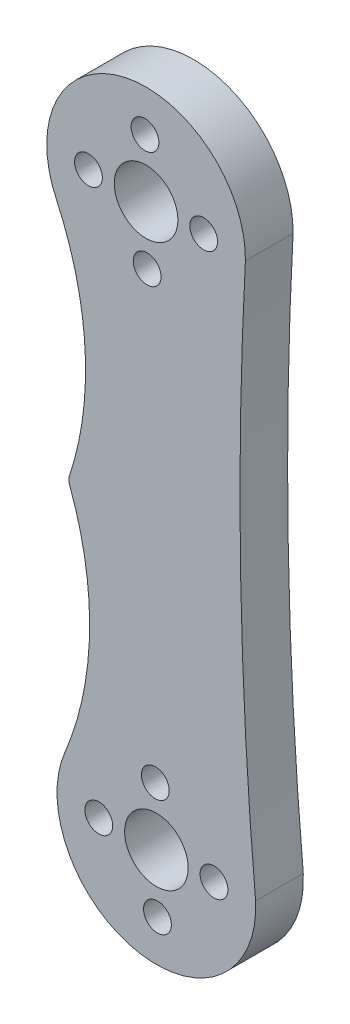
SolidWorks part; units mm, degrees
material "ABS"
ref_plane "Front Plane" through (0, 0, 0) normal (0, 0, 1) x (1, 0, 0)
ref_plane "Top Plane" through (0, 0, 0) normal (0, 1, 0) x (1, 0, 0)
ref_plane "Right Plane" through (0, 0, 0) normal (1, 0, 0) x (0, 0, -1)
sketch "Sketch1" plane through (0, 0, 0) normal (0, 0, 1) x (1, 0, 0)
  line L1 (-15, -50) -> (15, -50)
  line L2 (-15, -50) -> (-15, 50)
  line L3 (-15, 50) -> (15, 50)
  line L4 (15, -50) -> (15, 50)
  line L5 (-15, -50) -> (15, 50) construction
  line L6 (-15, 50) -> (15, -50) construction
  point P0 (0, 0)
  dimension "D1" = 100
  dimension "D2" = 30
extrude "Boss-Extrude1" add sketch "Sketch1" along normal blind 6
sketch "Sketch2" plane through (0, 0, 0) normal (0, 0, -1) x (-1, 0, 0)
  line L0 (-15, 50) -> (15, 50)
  line L1 (15, 50) -> (15, -50)
  line L2 (15, -50) -> (-15, -50)
  line L3 (-15, -50) -> (-15, 50)
  arc A0 (-11.5325, 35.4338) -> (13.1458, 32.8353) centre (0.9658, 35.6453) cw
  arc A1 (13.4636, 35.4133) -> (-11.5321, 35.8772) centre (0.9658, 35.6453) ccw construction
  arc A2 (12.3021, 30.3787) -> (13.4636, 35.4133) centre (0.9658, 35.6453) ccw construction
  arc A3 (13.1458, 32.8353) -> (12.3021, 30.3787) centre (0.9658, 35.6453) cw
  arc A4 (12.3021, 30.3787) -> (10.604, 0.9581) centre (48.5784, 13.5255) ccw
  arc A5 (8.5853, 14.2678) -> (10.604, 0.9581) centre (48.5784, 13.5255) ccw construction
  arc A6 (10.604, 0.9581) -> (10.5855, -0.037) centre (9.1799, 0.4868) cw
  arc A7 (10.5855, -0.037) -> (8.0744, -13.2627) centre (48.0675, -14.0049) ccw construction
  arc A8 (-12.815, -33.6676) -> (11.1908, -29.5004) centre (-0.3332, -34.3427) ccw
  arc A9 (-12.8311, -34.1107) -> (12.1646, -34.5746) centre (-0.3332, -34.3427) ccw construction
  arc A10 (12.1646, -34.5746) -> (11.1908, -29.5004) centre (-0.3332, -34.3427) ccw construction
  arc A11 (11.1908, -29.5004) -> (10.5855, -0.037) centre (48.0675, -14.0049) cw
  arc A13 (-11.5325, 35.4338) -> (-12.815, -33.6676) centre (-492.0571, 9.7897) cw
  arc A14 (-12.7832, -33.2253) -> (-12.8311, -34.1107) centre (-0.3332, -34.3427) ccw construction
  arc A15 (8.0744, -13.2627) -> (11.1908, -29.5004) centre (48.0675, -14.0049) ccw construction
  arc A16 (12.3021, 30.3787) -> (13.4636, 35.4133) centre (0.9658, 35.6453) ccw construction
  circle A17 centre (0.9658, 35.6453) radius 4
  circle A18 centre (1.1003, 42.894) radius 1.75
  circle A19 centre (8.2145, 35.5107) radius 1.75
  circle A20 centre (-6.283, 35.7798) radius 1.75
  circle A21 centre (0.8312, 28.3965) radius 1.75
  circle A22 centre (-0.3332, -34.3427) radius 4
  circle A23 centre (-0.1987, -27.0939) radius 1.75
  circle A24 centre (6.9155, -34.4772) radius 1.75
  circle A25 centre (-0.4677, -41.5914) radius 1.75
  circle A26 centre (-7.582, -34.2081) radius 1.75
  line M5 (-15, 50) -> (-15, -50)
  line M6 (-15, -50) -> (15, -50)
  line M7 (15, -50) -> (15, 50)
  line M8 (15, 50) -> (-15, 50)
extrude "Cut-Extrude1" cut sketch "Sketch2" against normal blind 6 contours A13 A0 A3 A4 A6 A11 A8 M8 M5 M6 M7 | A17 | A18 | A19 | A21 | A20 | A22 | A23 | A24 | A26 | A25 region at (0, 48.956, 0) region at (-0.9658, 35.6453, 0) region at (-1.1003, 42.894, 0) region at (-8.2145, 35.5107, 0) region at (6.283, 35.7798, 0) region at (-0.8312, 28.3965, 0) region at (0.3332, -34.3427, 0) region at (0.1987, -27.0939, 0) region at (-6.9155, -34.4772, 0) region at (0.4677, -41.5914, 0) region at (7.582, -34.2081, 0)
